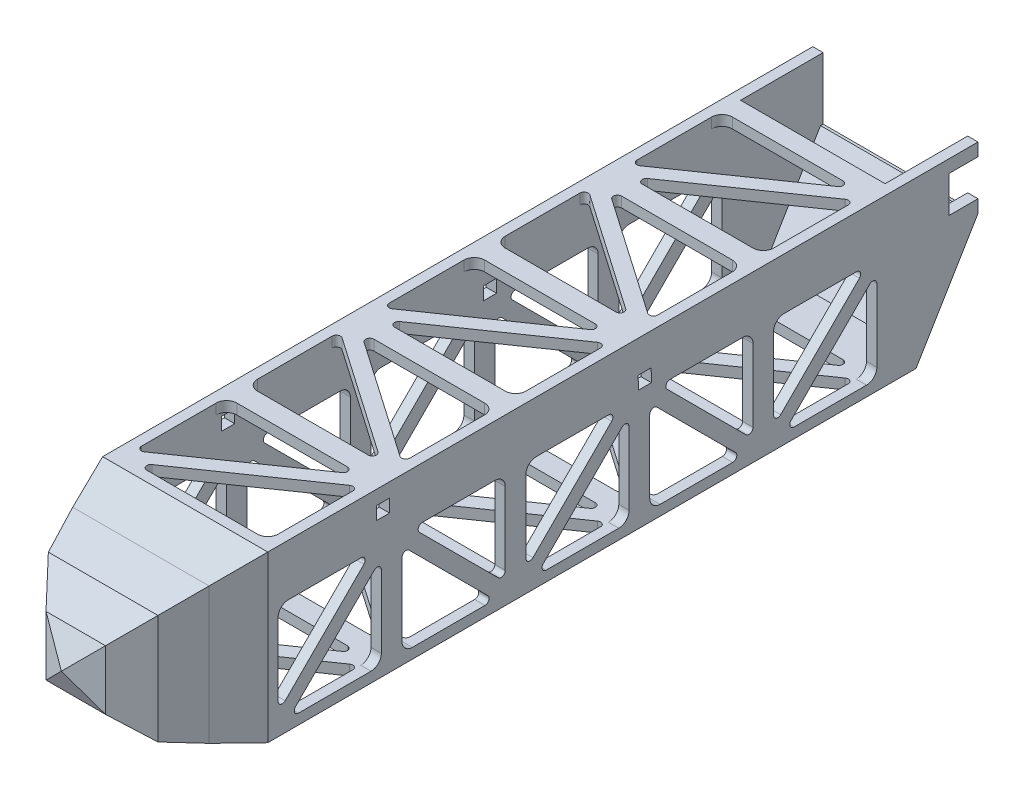
SolidWorks part; units mm, degrees
material "Balsa"
ref_plane "Front Plane" through (0, 0, 0) normal (0, 0, 1) x (1, 0, 0)
ref_plane "Top Plane" through (0, 0, 0) normal (0, 1, 0) x (1, 0, 0)
ref_plane "Right Plane" through (0, 0, 0) normal (1, 0, 0) x (0, 0, -1)
sketch "Sketch1" plane through (0, 0, 0) normal (0, 0, 1) x (1, 0, 0)
  line L1 (-50.8, -50.8) -> (50.8, -50.8)
  line L2 (-50.8, -50.8) -> (-50.8, 50.8)
  line L3 (-50.8, 50.8) -> (50.8, 50.8)
  line L4 (50.8, -50.8) -> (50.8, 50.8)
  line L5 (-50.8, -50.8) -> (50.8, 50.8) construction
  line L6 (-50.8, 50.8) -> (50.8, -50.8) construction
  point P0 (0, 0)
  dimension "D1" = 101.6
extrude "Boss-Extrude1" add sketch "Sketch1" along normal blind 436.88 contours L2 L1 L4 L3
ref_plane "Plane1" through (0, 0, 464.1566) normal (0, 0, 1) x (1, 0, 0)
sketch "Sketch3" plane through (0, 0, 464.1566) normal (0, 0, 1) x (1, 0, 0)
  line L1 (-41.9373, -41.9373) -> (41.9373, -41.9373)
  line L2 (-41.9373, -41.9373) -> (-41.9373, 41.9373)
  line L3 (-41.9373, 41.9373) -> (41.9373, 41.9373)
  line L4 (41.9373, -41.9373) -> (41.9373, 41.9373)
  line L5 (-41.9373, -41.9373) -> (41.9373, 41.9373) construction
  line L6 (-41.9373, 41.9373) -> (41.9373, -41.9373) construction
  point P0 (0, 0)
  dimension "D1" = 83.8746
  dimension "D2" = 83.8746
sketch "Sketch5" plane through (0, 0, 436.88) normal (0, 0, 1) x (1, 0, 0)
  line L0 (50.8, -50.8) -> (50.8, 50.8) construction
  line L1 (-50.8, 50.8) -> (50.8, 50.8) construction
  line L2 (-50.8, -50.8) -> (-50.8, 50.8) construction
  line L3 (-50.8, -50.8) -> (50.8, -50.8) construction
  line L4 (50.8, -50.8) -> (50.8, 50.8)
  line L5 (-50.8, 50.8) -> (50.8, 50.8)
  line L6 (-50.8, -50.8) -> (-50.8, 50.8)
  line L7 (-50.8, -50.8) -> (50.8, -50.8)
  dimension "D1" = 101.6
  dimension "D2" = 101.6
loft "Loft2" add profiles "Sketch5", "Sketch3" connector at (-50.8, 50.8, 436.88) connector at (-41.9373, 41.9373, 464.1566)
ref_plane "Plane2" through (0, 0, 487.3594) normal (0, 0, 1) x (1, 0, 0)
sketch "Sketch6" plane through (0, 0, 487.3594) normal (0, 0, 1) x (1, 0, 0)
  line L1 (-33.716, -33.716) -> (33.716, -33.716)
  line L2 (-33.716, -33.716) -> (-33.716, 33.716)
  line L3 (-33.716, 33.716) -> (33.716, 33.716)
  line L4 (33.716, -33.716) -> (33.716, 33.716)
  line L5 (-33.716, -33.716) -> (33.716, 33.716) construction
  line L6 (-33.716, 33.716) -> (33.716, -33.716) construction
  point P0 (0, 0)
loft "Loft3" add profiles "Sketch3<6>", "Sketch6" connector at (-41.9373, 41.9373, 464.1566) connector at (-33.716, 33.716, 487.3594)
sketch "Sketch3<6>" plane through (0, 0, 464.1566) normal (0, 0, 1) x (1, 0, 0) same geometry as "Sketch3"
ref_plane "Plane3" through (0, 0, 504.2173) normal (0, 0, 1) x (1, 0, 0)
sketch "Sketch7" plane through (0, 0, 504.2173) normal (0, 0, 1) x (1, 0, 0)
  line L5 (-41.9373, -41.9373) -> (41.9373, 41.9373) construction
  line L6 (-18.3041, -18.3041) -> (18.3041, -18.3041)
  line L8 (-18.3041, -18.3041) -> (-18.3041, 18.3041)
  line L9 (-18.3041, 18.3041) -> (18.3041, 18.3041)
  line L10 (18.3041, -18.3041) -> (18.3041, 18.3041)
  line L11 (-18.3041, -18.3041) -> (18.3041, 18.3041) construction
  line L12 (-18.3041, 18.3041) -> (18.3041, -18.3041) construction
  point P1 (0, 0)
loft "Loft4" add profiles "Sketch6<4>", "Sketch7" connector at (33.716, 33.716, 487.3594) connector at (18.3041, 18.3041, 504.2173)
sketch "Sketch6<4>" plane through (0, 0, 487.3594) normal (0, 0, 1) x (1, 0, 0) same geometry as "Sketch6"
sketch3d "3DSketch1" plane through (0, 0, 0) normal (0, 0, 1) x (1, 0, 0)
  dimension "D1" = 8.8627
sketch "Sketch8" plane through (0, 0, 513.08) normal (0, 0, 1) x (1, 0, 0)
  point P0 (0, 0)
loft "Loft5" add profiles "Sketch8", "Sketch7<5>"
sketch "Sketch7<5>" plane through (0, 0, 504.2173) normal (0, 0, 1) x (1, 0, 0) same geometry as "Sketch7"
shell "Shell1" thickness 6.35 removed face at (0, 0, 0)
sketch "Sketch10" plane through (50.8, 0, 0) normal (1, 0, 0) x (0, 0, -1)
  line L0 (-436.88, 50.8) -> (0, 50.8) construction
  line L3 (0, 50.8) -> (-68.9584, 50.8)
  line L4 (-68.9584, -50.8) -> (-68.9584, 50.8)
  line L5 (0, 50.8) -> (0, 12.7)
  line L6 (0, -50.8) -> (-38.1, -50.8)
  line L7 (0, 12.7) -> (-38.1, -50.8)
  line L8 (0, 12.7) -> (0, -50.8)
  line M16 (0, -50.8) -> (0, 50.8)
  line M19 (-436.88, -50.8) -> (0, -50.8)
  dimension "D1" = 38.1
  dimension "D2" = 38.1
  dimension "D3" = 63.5
extrude "Cut-Extrude2" cut sketch "Sketch10" against normal through all contours L7 M16 M19 region at (50.8, -29.6333, 12.7)
sketch "Sketch11" plane through (50.8, 0, 0) normal (1, 0, 0) x (0, 0, -1)
  line L0 (-38.1, -50.8) -> (-39.6875, -50.8)
  line L1 (-436.88, -50.8) -> (-38.1, -50.8) construction
  line L2 (0, 50.8) -> (-1.5875, 50.8)
  line L3 (-436.88, 50.8) -> (0, 50.8) construction
  line L4 (-1.5875, 50.8) -> (-1.5875, 12.7)
  line L5 (0, 50.8) -> (0, 12.7)
  line L6 (-1.5875, 12.7) -> (-39.6875, -50.8)
  line L7 (0, 12.7) -> (-38.1, -50.8)
  dimension "D1" = 1.5875
  dimension "D2" = 1.5875
extrude "Boss-Extrude2" add sketch "Sketch11" against normal blind 101.6
sketch "Sketch12" plane through (0, 0, 0) normal (0, 0, -1) x (-1, 0, 0)
  line L0 (-50.8, 50.8) -> (-44.45, 50.8)
  line L1 (50.8, 50.8) -> (-50.8, 50.8) construction
  line L2 (50.8, 12.7) -> (-50.8, 12.7) construction
  line L3 (-44.45, 50.8) -> (44.45, 50.8)
  line L4 (-44.45, 50.8) -> (-44.45, 12.7)
  line L5 (-44.45, 12.7) -> (44.45, 12.7)
  line L6 (44.45, 50.8) -> (44.45, 12.7)
  line M7 (-50.8, 12.7) -> (50.8, 12.7)
  line M9 (50.8, 50.8) -> (-50.8, 50.8)
  dimension "D1" = 6.35
  dimension "D2" = 88.9
extrude "Cut-Extrude3" cut sketch "Sketch12" against normal blind 50.8 contours L6 L4 M9 M7 region at (0, 31.75, 0)
sketch "Sketch15" plane through (50.8, 0, 0) normal (1, 0, 0) x (0, 0, -1)
  line L0 (0, 12.7) -> (0, 50.8) construction
  line L1 (0, 42.926) -> (-17.78, 42.926)
  line L2 (0, 42.926) -> (0, 20.574)
  line L3 (0, 20.574) -> (-17.78, 20.574)
  line L4 (-17.78, 42.926) -> (-17.78, 20.574)
  line L5 (-436.88, 50.8) -> (0, 50.8) construction
  dimension "D1" = 17.78
  dimension "D2" = 22.352
  dimension "D3" = 7.874
extrude "Cut-Extrude5" cut sketch "Sketch15" against normal up to surface (6.35 mm away)
sketch "Sketch16" plane through (50.8, 0, 0) normal (1, 0, 0) x (0, 0, -1)
  line L0 (-436.88, -50.8) -> (-436.88, 50.8) construction
  line L1 (-424.18, 19.05) -> (-379.5121, 19.05)
  line L2 (-430.53, 12.7) -> (-430.53, -31.9679)
  line L3 (-418.0479, -44.45) -> (-373.38, -44.45)
  line L4 (-367.03, 6.5679) -> (-367.03, -38.1)
  line L5 (-436.88, -50.8) -> (-38.1, -50.8) construction
  line L6 (-354.33, 6.5679) -> (-354.33, -38.1)
  line L7 (-341.8479, 19.05) -> (-297.18, 19.05)
  line L8 (-290.83, 12.7) -> (-290.83, -31.9679)
  line L9 (-347.98, -44.45) -> (-303.3121, -44.45)
  line L10 (-278.13, 12.7) -> (-278.13, -31.9679)
  line L11 (-271.78, 19.05) -> (-227.1121, 19.05)
  line L12 (-214.63, 6.5679) -> (-214.63, -38.1)
  line L13 (-265.6479, -44.45) -> (-220.98, -44.45)
  line L14 (-201.93, 6.5679) -> (-201.93, -38.1)
  line L15 (-189.4479, 19.05) -> (-144.78, 19.05)
  line L16 (-138.43, 12.7) -> (-138.43, -31.9679)
  line L17 (-195.58, -44.45) -> (-150.9121, -44.45)
  line L18 (-125.73, 12.7) -> (-125.73, -31.9679)
  line L19 (-119.38, 19.05) -> (-74.7121, 19.05)
  line L20 (-62.23, 6.5679) -> (-62.23, -38.1)
  line L21 (-113.2479, -44.45) -> (-68.58, -44.45)
  line L22 (-377.7161, 14.7139) -> (-426.1939, -33.7639)
  line L23 (-419.8439, -40.1139) -> (-371.3661, 8.3639)
  line L24 (-349.9939, 8.3639) -> (-301.5161, -40.1139)
  line L25 (-343.6439, 14.7139) -> (-295.1661, -33.7639)
  line L26 (-273.7939, -33.7639) -> (-225.3161, 14.7139)
  line L27 (-218.9661, 8.3639) -> (-267.4439, -40.1139)
  line L28 (-197.5939, 8.3639) -> (-149.1161, -40.1139)
  line L29 (-142.7661, -33.7639) -> (-191.2439, 14.7139)
  line L30 (-121.3939, -33.7639) -> (-72.9161, 14.7139)
  line L31 (-66.5661, 8.3639) -> (-115.0439, -40.1139)
  arc A0 (-430.53, -38.1) -> (-424.18, -44.45) centre (-424.18, -38.1) ccw
  arc A1 (-373.38, -44.45) -> (-367.03, -38.1) centre (-373.38, -38.1) ccw
  arc A2 (-373.38, 19.05) -> (-367.03, 12.7) centre (-373.38, 12.7) cw
  arc A3 (-424.18, 19.05) -> (-430.53, 12.7) centre (-424.18, 12.7) ccw
  arc A4 (-347.98, 19.05) -> (-354.33, 12.7) centre (-347.98, 12.7) ccw
  arc A5 (-354.33, -38.1) -> (-347.98, -44.45) centre (-347.98, -38.1) ccw
  arc A6 (-297.18, 19.05) -> (-290.83, 12.7) centre (-297.18, 12.7) cw
  arc A7 (-297.18, -44.45) -> (-290.83, -38.1) centre (-297.18, -38.1) ccw
  arc A8 (-271.78, 19.05) -> (-278.13, 12.7) centre (-271.78, 12.7) ccw
  arc A9 (-278.13, -38.1) -> (-271.78, -44.45) centre (-271.78, -38.1) ccw
  arc A10 (-220.98, 19.05) -> (-214.63, 12.7) centre (-220.98, 12.7) cw
  arc A11 (-220.98, -44.45) -> (-214.63, -38.1) centre (-220.98, -38.1) ccw
  arc A12 (-195.58, 19.05) -> (-201.93, 12.7) centre (-195.58, 12.7) ccw
  arc A13 (-201.93, -38.1) -> (-195.58, -44.45) centre (-195.58, -38.1) ccw
  arc A14 (-144.78, 19.05) -> (-138.43, 12.7) centre (-144.78, 12.7) cw
  arc A15 (-144.78, -44.45) -> (-138.43, -38.1) centre (-144.78, -38.1) ccw
  arc A16 (-119.38, 19.05) -> (-125.73, 12.7) centre (-119.38, 12.7) ccw
  arc A17 (-125.73, -38.1) -> (-119.38, -44.45) centre (-119.38, -38.1) ccw
  arc A18 (-68.58, 19.05) -> (-62.23, 12.7) centre (-68.58, 12.7) cw
  arc A19 (-68.58, -44.45) -> (-62.23, -38.1) centre (-68.58, -38.1) ccw
  arc A20 (-74.7121, 19.05) -> (-72.9161, 14.7139) centre (-74.7121, 16.51) cw
  arc A21 (-66.5661, 8.3639) -> (-62.23, 6.5679) centre (-64.77, 6.5679) cw
  arc A22 (-115.0439, -40.1139) -> (-113.2479, -44.45) centre (-113.2479, -41.91) ccw
  arc A23 (-121.3939, -33.7639) -> (-125.73, -31.9679) centre (-123.19, -31.9679) cw
  arc A24 (-150.9121, -44.45) -> (-149.1161, -40.1139) centre (-150.9121, -41.91) ccw
  arc A25 (-142.7661, -33.7639) -> (-138.43, -31.9679) centre (-140.97, -31.9679) ccw
  arc A26 (-189.4479, 19.05) -> (-191.2439, 14.7139) centre (-189.4479, 16.51) ccw
  arc A27 (-197.5939, 8.3639) -> (-201.93, 6.5679) centre (-199.39, 6.5679) ccw
  arc A28 (-227.1121, 19.05) -> (-225.3161, 14.7139) centre (-227.1121, 16.51) cw
  arc A29 (-218.9661, 8.3639) -> (-214.63, 6.5679) centre (-217.17, 6.5679) cw
  arc A30 (-265.6479, -44.45) -> (-267.4439, -40.1139) centre (-265.6479, -41.91) cw
  arc A31 (-278.13, -31.9679) -> (-273.7939, -33.7639) centre (-275.59, -31.9679) ccw
  arc A32 (-303.3121, -44.45) -> (-301.5161, -40.1139) centre (-303.3121, -41.91) ccw
  arc A33 (-290.83, -31.9679) -> (-295.1661, -33.7639) centre (-293.37, -31.9679) cw
  arc A34 (-341.8479, 19.05) -> (-343.6439, 14.7139) centre (-341.8479, 16.51) ccw
  arc A35 (-349.9939, 8.3639) -> (-354.33, 6.5679) centre (-351.79, 6.5679) ccw
  arc A36 (-367.03, 6.5679) -> (-371.3661, 8.3639) centre (-369.57, 6.5679) ccw
  arc A37 (-418.0479, -44.45) -> (-419.8439, -40.1139) centre (-418.0479, -41.91) cw
  arc A38 (-377.7161, 14.7139) -> (-379.5121, 19.05) centre (-379.5121, 16.51) ccw
  arc A39 (-426.1939, -33.7639) -> (-430.53, -31.9679) centre (-427.99, -31.9679) cw
  point P12 (-367.03, -44.45)
  point P15 (-367.03, 19.05)
  point P18 (-430.53, 19.05)
  dimension "D1" = 6.35
  dimension "D5" = 6.35
  dimension "D7" = 2.54
  dimension "D2" = 6.35
  dimension "D3" = 63.5
  dimension "D4" = 63.5
  dimension "D6" = 5
extrude "Cut-Extrude6" cut sketch "Sketch16" against normal up to surface (101.6 mm away) contours L1 A3 L2 L22 | L3 A1 L4 L23 | L6 A5 L9 L24 | A6 L7 L25 L8 | L11 A8 L10 L26 | L13 A11 L12 L27 | L14 A13 L17 L28 | A14 L15 L29 L16 | L21 A19 L20 L31 | L19 A16 L18 L30 region at (50.8, -0.0083, 411.4717) region at (50.8, -25.3917, 386.0883) region at (50.8, -25.3917, 335.2717) region at (50.8, -0.0083, 309.8883) region at (50.8, -0.0083, 259.0717) region at (50.8, -25.3917, 233.6883) region at (50.8, -25.3917, 182.8717) region at (50.8, -0.0083, 157.4883) region at (50.8, -0.0083, 106.6717) region at (50.8, -25.3917, 81.2883) up to face at (-50.8, 2.54, 182.372)
sketch "Sketch17" plane through (0, 50.8, 0) normal (0, 1, 0) x (1, 0, 0)
  line L0 (50.8, -436.88) -> (50.8, 0) construction
  line L1 (38.1, -430.53) -> (-22.2093, -430.53)
  line L2 (44.45, -424.18) -> (44.45, -382.8539)
  line L3 (22.2093, -367.03) -> (-38.1, -367.03)
  line L4 (-44.45, -414.7061) -> (-44.45, -373.38)
  line L5 (-50.8, -436.88) -> (50.8, -436.88) construction
  line L6 (-50.8, -436.88) -> (-50.8, 0) construction
  line L7 (44.45, -344.747) -> (44.45, -303.4209)
  line L8 (22.2093, -360.5709) -> (-38.1, -360.5709)
  line L9 (-44.45, -354.2209) -> (-44.45, -306.6045)
  line L11 (44.45, -284.2618) -> (44.45, -236.6454)
  line L12 (38.1, -290.6118) -> (-32.7601, -290.6118)
  line L13 (-44.45, -281.0782) -> (-44.45, -233.4618)
  line L14 (37.5789, -227.1118) -> (-38.1, -227.1118)
  line L15 (44.45, -211.1191) -> (44.45, -163.5027)
  line L16 (32.7601, -220.6527) -> (-38.1, -220.6527)
  line L17 (-44.45, -214.3027) -> (-44.45, -166.6863)
  line L19 (44.45, -144.3436) -> (44.45, -98.3913)
  line L20 (38.1, -150.6936) -> (-37.3066, -150.6936)
  line L21 (-44.45, -139.4958) -> (-44.45, -93.5436)
  line L22 (29.9688, -87.1936) -> (-38.1, -87.1936)
  line L23 (-36.6606, -418.7874) -> (25.0348, -376.0751)
  line L24 (38.1, -367.03) -> (44.45, -373.38)
  line L25 (-25.0348, -421.4849) -> (36.6606, -378.7726)
  line L26 (36.6606, -348.8283) -> (-31.4146, -301.6993)
  line L27 (-41.8325, -305.233) -> (25.0348, -351.5257)
  line L28 (-33.7096, -287.5723) -> (41.8325, -235.2739)
  line L29 (38.5284, -226.8152) -> (-41.8325, -282.4497)
  line L30 (33.7096, -217.6132) -> (-41.8325, -165.3148)
  line L31 (-31.4146, -161.7811) -> (41.8325, -212.4906)
  line L32 (-38.7524, -151.1452) -> (40.4642, -96.303)
  line L33 (31.4146, -91.822) -> (-40.4642, -141.5842)
  line L35 (38.1, -157.1527) -> (-37.3066, -157.1527) [skipped]
  line L36 (38.1, -157.1527) -> (35.6588, -123.3001)
  line L37 (-29.9688, -157.1527) -> (38.1, -157.1527)
  line L38 (-29.9688, -297.0709) -> (38.1, -297.0709)
  line L39 (38.1, -297.0709) -> (-36.5494, -297.0709) [skipped]
  arc A0 (44.45, -373.38) -> (38.1, -367.03) centre (38.1, -373.38) ccw
  arc A1 (38.1, -430.53) -> (44.45, -424.18) centre (38.1, -424.18) ccw
  arc A2 (-38.1, -430.53) -> (-44.45, -424.18) centre (-38.1, -424.18) cw
  arc A3 (-38.1, -367.03) -> (-44.45, -373.38) centre (-38.1, -373.38) ccw
  arc A4 (38.1, -360.5709) -> (44.45, -354.2209) centre (38.1, -354.2209) ccw
  arc A5 (44.45, -303.4209) -> (38.1, -297.0709) centre (38.1, -303.4209) ccw
  arc A6 (-38.1, -360.5709) -> (-44.45, -354.2209) centre (-38.1, -354.2209) cw
  arc A7 (-38.1, -297.0709) -> (-44.45, -303.4209) centre (-38.1, -303.4209) ccw
  arc A8 (38.1, -290.6118) -> (44.45, -284.2618) centre (38.1, -284.2618) ccw
  arc A9 (44.45, -233.4618) -> (38.1, -227.1118) centre (38.1, -233.4618) ccw
  arc A10 (-38.1, -290.6118) -> (-44.45, -284.2618) centre (-38.1, -284.2618) cw
  arc A11 (-38.1, -227.1118) -> (-44.45, -233.4618) centre (-38.1, -233.4618) ccw
  arc A12 (38.1, -220.6527) -> (44.45, -214.3027) centre (38.1, -214.3027) ccw
  arc A13 (44.45, -163.5027) -> (38.1, -157.1527) centre (38.1, -163.5027) ccw
  arc A14 (-38.1, -220.6527) -> (-44.45, -214.3027) centre (-38.1, -214.3027) cw
  arc A16 (38.1, -150.6936) -> (44.45, -144.3436) centre (38.1, -144.3436) ccw
  arc A17 (44.45, -93.5436) -> (38.1, -87.1936) centre (38.1, -93.5436) ccw
  arc A18 (-38.1, -150.6936) -> (-44.45, -144.3436) centre (-38.1, -144.3436) cw
  arc A19 (-38.1, -87.1936) -> (-44.45, -93.5436) centre (-38.1, -93.5436) ccw
  arc A20 (-40.4642, -141.5842) -> (-44.45, -139.4958) centre (-41.91, -139.4958) cw
  arc A21 (31.4146, -91.822) -> (29.9688, -87.1936) centre (29.9688, -89.7336) ccw
  arc A22 (40.4642, -96.303) -> (44.45, -98.3913) centre (41.91, -98.3913) cw
  arc A23 (-38.7524, -151.1452) -> (-37.3066, -150.6936) centre (-37.3066, -153.2336) ccw
  arc A25 (-41.8325, -165.3148) -> (-44.45, -166.6863) centre (-42.7819, -166.6863) ccw
  arc A26 (44.45, -211.1191) -> (41.8325, -212.4906) centre (42.7819, -211.1191) cw
  arc A27 (33.7096, -217.6132) -> (32.7601, -220.6527) centre (32.7601, -218.9846) cw
  arc A28 (37.5789, -227.1118) -> (38.5284, -226.8152) centre (37.5789, -225.4437) cw
  arc A29 (41.8325, -235.2739) -> (44.45, -236.6454) centre (42.7819, -236.6454) cw
  arc A30 (-32.7601, -290.6118) -> (-33.7096, -287.5723) centre (-32.7601, -288.9437) cw
  arc A31 (-41.8325, -282.4497) -> (-44.45, -281.0782) centre (-42.7819, -281.0782) cw
  arc A32 (-44.45, -306.6045) -> (-41.8325, -305.233) centre (-42.7819, -306.6045) cw
  arc A34 (44.45, -344.747) -> (36.6606, -348.8283) centre (39.4861, -344.747) cw
  arc A35 (22.2093, -360.5709) -> (25.0348, -351.5257) centre (22.2093, -355.607) ccw
  arc A36 (44.45, -382.8539) -> (36.6606, -378.7726) centre (39.4861, -382.8539) ccw
  arc A37 (25.0348, -376.0751) -> (22.2093, -367.03) centre (22.2093, -371.9939) ccw
  arc A38 (-44.45, -414.7061) -> (-36.6606, -418.7874) centre (-39.4861, -414.7061) ccw
  arc A39 (-22.2093, -430.53) -> (-25.0348, -421.4849) centre (-22.2093, -425.5661) cw
  arc A40 (-38.1, -157.1527) -> (-44.45, -163.5027) centre (-38.1, -163.5027) ccw [skipped]
  arc A41 (-31.4146, -161.7811) -> (-29.9688, -157.1527) centre (-29.9688, -159.6927) cw
  arc A42 (-31.4146, -301.6993) -> (-29.9688, -297.0709) centre (-29.9688, -299.6109) cw
  point P16 (-44.45, -430.53)
  point P19 (-44.45, -367.03)
  dimension "D1" = 6.35
  dimension "D5" = 6.35
  dimension "D7" = 2.54
  dimension "D2" = 6.35
  dimension "D4" = 63.5
  dimension "D6" = 5
  dimension "D8" = 2.54
  dimension "D9" = 2.54
  dimension "D3" = 6.35
sketch "Sketch18" plane through (0, 50.8, 0) normal (0, 1, 0) x (1, 0, 0)
  line L0 (-50.8, -436.88) -> (-50.8, 0) construction
  line L1 (38.1, -430.53) -> (-29.9688, -430.53)
  line L2 (44.45, -424.18) -> (44.45, -378.2278)
  line L3 (29.9688, -367.03) -> (-38.1, -367.03)
  line L4 (-44.45, -419.3322) -> (-44.45, -373.38)
  line L5 (50.8, -436.88) -> (50.8, 0) construction
  line L6 (-50.8, -436.88) -> (50.8, -436.88) construction
  line L7 (-40.4642, -299.9394) -> (31.4146, -349.7016)
  line L8 (-38.1, -354.33) -> (29.9688, -354.33)
  line L9 (-44.45, -347.98) -> (-44.45, -302.0278)
  line L10 (-29.9688, -290.83) -> (38.1, -290.83)
  line L11 (44.45, -343.1322) -> (44.45, -297.18)
  line L12 (40.4642, -345.2206) -> (-31.4146, -295.4584)
  line L13 (31.4146, -371.6584) -> (-40.4642, -421.4206)
  line L14 (-31.4146, -425.9016) -> (40.4642, -376.1394)
  line L15 (38.1, -278.13) -> (-29.9688, -278.13)
  line L16 (44.45, -271.78) -> (44.45, -225.8278)
  line L17 (-31.4146, -273.5016) -> (40.4642, -223.7394)
  line L18 (31.4146, -219.2584) -> (-40.4642, -269.0206)
  line L19 (29.9688, -214.63) -> (-38.1, -214.63)
  line L20 (-44.45, -266.9322) -> (-44.45, -220.98)
  line L21 (-38.1, -201.93) -> (29.9688, -201.93)
  line L22 (-44.45, -195.58) -> (-44.45, -149.6278)
  line L23 (-40.4642, -147.5394) -> (31.4146, -197.3016)
  line L24 (40.4642, -192.8206) -> (-31.4146, -143.0584)
  line L25 (-29.9688, -138.43) -> (38.1, -138.43)
  line L26 (44.45, -190.7322) -> (44.45, -144.78)
  line L27 (38.1, -125.73) -> (-29.9688, -125.73)
  line L28 (44.45, -119.38) -> (44.45, -73.4278)
  line L29 (-31.4146, -121.1016) -> (40.4642, -71.3394)
  line L30 (31.4146, -66.8584) -> (-40.4642, -116.6206)
  line L31 (29.9688, -62.23) -> (-38.1, -62.23)
  line L32 (-44.45, -114.5322) -> (-44.45, -68.58)
  line L39 (-38.1, -49.53) -> (29.9688, -49.53) [skipped]
  line L40 (-40.4642, 4.8606) -> (31.4146, -44.9016) [skipped]
  line L41 (-44.45, -43.18) -> (-44.45, 2.7722) [skipped]
  line L42 (40.4642, -40.4206) -> (-31.4146, 9.3416) [skipped]
  line L43 (-29.9688, 13.97) -> (38.1, 13.97) [skipped]
  line L44 (44.45, -38.3322) -> (44.45, 7.62) [skipped]
  arc A0 (38.1, -430.53) -> (44.45, -424.18) centre (38.1, -424.18) ccw
  arc A3 (-38.1, -367.03) -> (-44.45, -373.38) centre (-38.1, -373.38) ccw
  arc A4 (-38.1, -354.33) -> (-44.45, -347.98) centre (-38.1, -347.98) cw
  arc A6 (38.1, -290.83) -> (44.45, -297.18) centre (38.1, -297.18) cw
  arc A8 (44.45, -343.1322) -> (40.4642, -345.2206) centre (41.91, -343.1322) cw
  arc A9 (-29.9688, -290.83) -> (-31.4146, -295.4584) centre (-29.9688, -293.37) ccw
  arc A10 (-44.45, -302.0278) -> (-40.4642, -299.9394) centre (-41.91, -302.0278) cw
  arc A11 (29.9688, -354.33) -> (31.4146, -349.7016) centre (29.9688, -351.79) ccw
  arc A12 (44.45, -378.2278) -> (40.4642, -376.1394) centre (41.91, -378.2278) ccw
  arc A13 (29.9688, -367.03) -> (31.4146, -371.6584) centre (29.9688, -369.57) cw
  arc A14 (-29.9688, -430.53) -> (-31.4146, -425.9016) centre (-29.9688, -427.99) cw
  arc A15 (-44.45, -419.3322) -> (-40.4642, -421.4206) centre (-41.91, -419.3322) ccw
  arc A16 (-29.9688, -278.13) -> (-31.4146, -273.5016) centre (-29.9688, -275.59) cw
  arc A17 (38.1, -278.13) -> (44.45, -271.78) centre (38.1, -271.78) ccw
  arc A18 (44.45, -225.8278) -> (40.4642, -223.7394) centre (41.91, -225.8278) ccw
  arc A19 (-44.45, -266.9322) -> (-40.4642, -269.0206) centre (-41.91, -266.9322) ccw
  arc A20 (29.9688, -214.63) -> (31.4146, -219.2584) centre (29.9688, -217.17) cw
  arc A21 (-38.1, -214.63) -> (-44.45, -220.98) centre (-38.1, -220.98) ccw
  arc A22 (29.9688, -201.93) -> (31.4146, -197.3016) centre (29.9688, -199.39) ccw
  arc A23 (-38.1, -201.93) -> (-44.45, -195.58) centre (-38.1, -195.58) cw
  arc A24 (-44.45, -149.6278) -> (-40.4642, -147.5394) centre (-41.91, -149.6278) cw
  arc A25 (-29.9688, -138.43) -> (-31.4146, -143.0584) centre (-29.9688, -140.97) ccw
  arc A26 (44.45, -190.7322) -> (40.4642, -192.8206) centre (41.91, -190.7322) cw
  arc A27 (38.1, -138.43) -> (44.45, -144.78) centre (38.1, -144.78) cw
  arc A28 (-29.9688, -125.73) -> (-31.4146, -121.1016) centre (-29.9688, -123.19) cw
  arc A29 (38.1, -125.73) -> (44.45, -119.38) centre (38.1, -119.38) ccw
  arc A30 (44.45, -73.4278) -> (40.4642, -71.3394) centre (41.91, -73.4278) ccw
  arc A31 (-44.45, -114.5322) -> (-40.4642, -116.6206) centre (-41.91, -114.5322) ccw
  arc A32 (29.9688, -62.23) -> (31.4146, -66.8584) centre (29.9688, -64.77) cw
  arc A33 (-38.1, -62.23) -> (-44.45, -68.58) centre (-38.1, -68.58) ccw
  arc A40 (29.9688, -49.53) -> (31.4146, -44.9016) centre (29.9688, -46.99) ccw [skipped]
  arc A41 (-44.45, 2.7722) -> (-40.4642, 4.8606) centre (-41.91, 2.7722) cw [skipped]
  arc A42 (-38.1, -49.53) -> (-44.45, -43.18) centre (-38.1, -43.18) cw [skipped]
  arc A43 (-29.9688, 13.97) -> (-31.4146, 9.3416) centre (-29.9688, 11.43) ccw [skipped]
  arc A44 (38.1, 13.97) -> (44.45, 7.62) centre (38.1, 7.62) cw [skipped]
  arc A45 (44.45, -38.3322) -> (40.4642, -40.4206) centre (41.91, -38.3322) cw [skipped]
  point P12 (44.45, -430.53)
  point P15 (44.45, -367.03)
  point P28 (44.45, -354.33)
  point P31 (44.45, -290.83)
  dimension "D1" = 6.35
  dimension "D5" = 6.35
  dimension "D2" = 6.35
  dimension "D4" = 63.5
  dimension "D3" = 6.35
  dimension "D10" = 6.35
  dimension "D11" = 2.54
  dimension "D6" = 12.7
  dimension "D8" = 6.35
  dimension "D9" = 6.35
  dimension "D12" = 3
extrude "Cut-Extrude9" cut sketch "Sketch18" against normal up to surface (101.6 mm away) up to face at (0, -50.8, 237.49)
ref_plane "Plane4" through (0, 38.1, 0) normal (0, 1, 0) x (1, 0, 0)
ref_plane "Plane5" through (0, -4.6068, 436.295) normal (0, -0.0106, 0.9999) x (1, 0, 0)
sketch "Sketch19" plane through (-50.8, 0, 0) normal (-1, 0, 0) x (0, 0, 1)
  line L0 (361.9883, 34.0995) -> (361.9883, 42.1005)
  line L1 (361.9883, 34.0995) -> (361.9883, 42.1005)
  line L2 (361.9883, 42.1005) -> (369.9893, 42.1005)
  line L3 (361.9883, 42.1005) -> (369.9893, 42.1005)
  line L4 (369.9893, 42.1005) -> (369.9893, 34.0995)
  line L5 (369.9893, 42.1005) -> (369.9893, 34.0995)
  line L6 (369.9893, 34.0995) -> (361.9883, 34.0995)
  line L7 (369.9893, 34.0995) -> (361.9883, 34.0995)
  line L8 (200.9418, 23.0654) -> (201.0263, 31.066)
  line L9 (200.9418, 23.0654) -> (201.0263, 31.066)
  line L10 (201.0263, 31.066) -> (209.0268, 30.9815)
  line L11 (201.0263, 31.066) -> (209.0268, 30.9815)
  line L12 (209.0268, 30.9815) -> (208.9424, 22.9809)
  line L13 (209.0268, 30.9815) -> (208.9424, 22.9809)
  line L14 (208.9424, 22.9809) -> (200.9418, 23.0654)
  line L15 (208.9424, 22.9809) -> (200.9418, 23.0654)
extrude "Cut-Extrude10" cut sketch "Sketch19" against normal through all
equation "\"Fuse_Diam\"= 4"
equation "\"D2@Sketch1\"=\"Fuse_Diam\""
equation "\"D1@Sketch1\"=\"Fuse_Diam\""
equation "\"Magic Line\"= 3 / ( cos ( 18 ) + cos ( 2 * 18 ) + cos ( 3 * 18 ) + cos ( 4 * 18 ) )"
equation "\"Second Stage Cone\"= 3.30215"
equation "\"D1@Sketch3\"=\"Second Stage Cone\""
equation "\"D2@Sketch3\"=\"Second Stage Cone\""
equation "\"Thick\"=0.25"
equation "\"D1@Sketch12\"=\"Thick\""
equation "\"D1@Shell1\"=\"Thick\""
equation "\"attachment\"=3.5"
equation "\"D2@Sketch12\"=\"attachment\""
equation "\"D2@Sketch16\"=\"Thick\""
equation "\"D1@Sketch16\"=0.25in"
equation "\"D1@Sketch17\"=\"Thick\""
equation "\"D2@Sketch17\"=\"Thick\""
equation "\"D3@Sketch17\"=\"Thick\""
equation "\"D1@Sketch18\"=\"Thick\""
equation "\"D2@Sketch18\"=\"Thick\""
